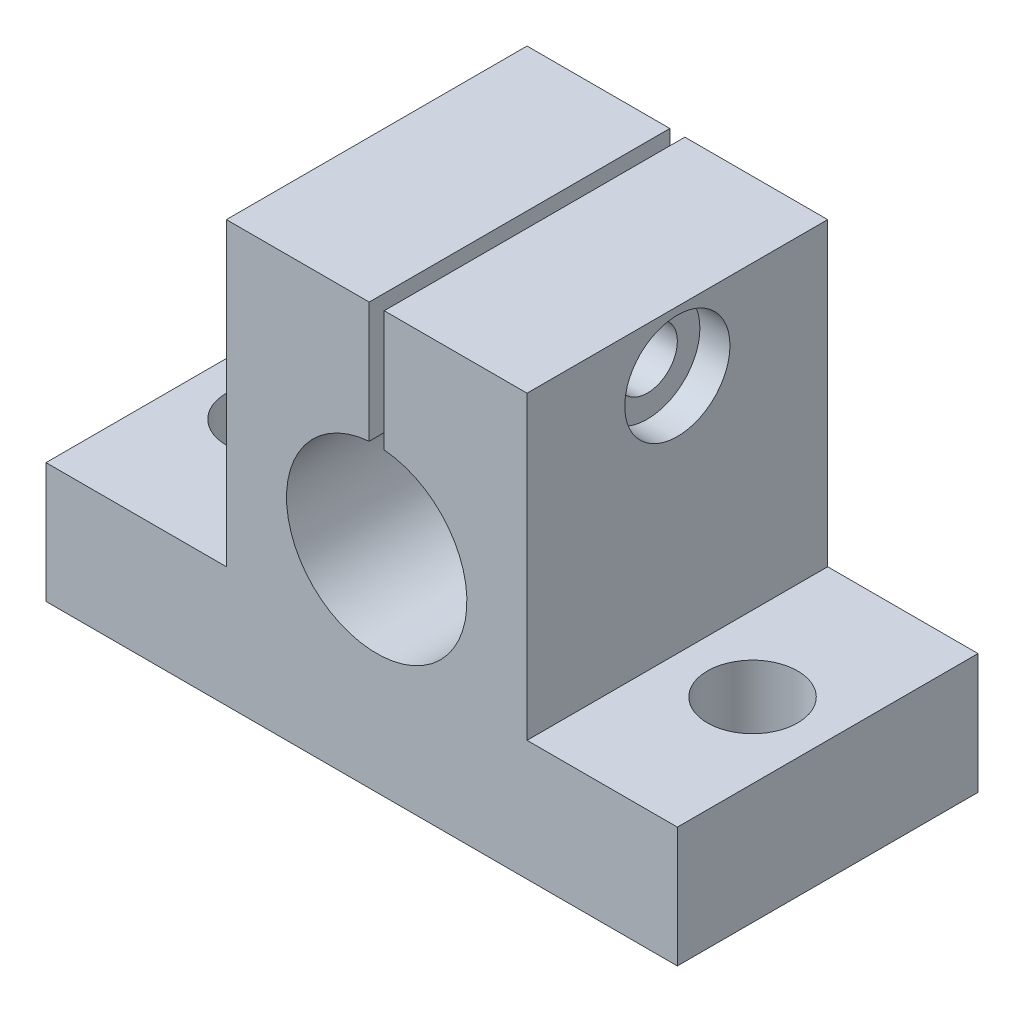
SolidWorks part; units mm, degrees
ref_plane "Спереди" through (0, 0, 0) normal (0, 0, 1) x (1, 0, 0)
ref_plane "Сверху" through (0, 0, 0) normal (0, 1, 0) x (1, 0, 0)
ref_plane "Справа" through (0, 0, 0) normal (1, 0, 0) x (0, 0, -1)
sketch "Эскиз1" plane through (0, 0, 0) normal (0, 0, 1) x (1, 0, 0)
  line L0 (0, 0) -> (0, 14) construction
  line L1 (-22, 0) -> (20, 0)
  line L2 (20, 0) -> (20, 8)
  line L3 (20, 8) -> (10, 8)
  line L4 (10, 8) -> (10, 28)
  line L5 (10, 28) -> (0.5, 28)
  line L6 (0.5, 28) -> (0.5, 19.9791)
  line L7 (-0.5, 19.9791) -> (-0.5, 28)
  line L8 (-0.5, 28) -> (-10, 28)
  line L9 (-10, 28) -> (-10, 8)
  line L10 (-10, 8) -> (-22, 8)
  line L11 (-22, 8) -> (-22, 0)
  arc A0 (-0.5, 19.9791) -> (0.5, 19.9791) centre (0, 14) ccw
  dimension "D1" = 6
  dimension "D2" = 1
  dimension "D3" = 8
  dimension "D4" = 42
  dimension "D5" = 14
  dimension "D6" = 20
  dimension "D7" = 14
  dimension "D8" = 6
extrude "Бобышка-Вытянуть1" add sketch "Эскиз1" along normal blind 20
sketch "Эскиз4" plane through (0, 8, 0) normal (0, 1, 0) x (1, 0, 0)
  line L0 (20, -20) -> (10, -20) construction
  line L1 (-10, -20) -> (-22, -20) construction
  line L2 (20, -20) -> (20, 0) construction
  line L3 (-22, -20) -> (-22, 0) construction
  circle A0 centre (15, -10) radius 3
  circle A1 centre (-17, -10) radius 3
  dimension "D1" = 6
  dimension "D2" = 6
  dimension "D3" = 10
  dimension "D4" = 10
  dimension "D5" = 5
  dimension "D6" = 5
extrude "Вырез-Вытянуть1" cut sketch "Эскиз4" against normal up to surface (8 mm away) up to face at (-1, 0, 10)
sketch "Эскиз5" plane through (10, 0, 0) normal (1, 0, 0) x (0, 0, -1)
  line L0 (-20, 8) -> (-20, 28) construction
  line L1 (-20, 28) -> (0, 28) construction
  circle A0 centre (-10, 24) radius 2
  dimension "D1" = 4
  dimension "D2" = 10
  dimension "D3" = 4
extrude "Вырез-Вытянуть2" cut sketch "Эскиз5" against normal up to surface (20 mm away) up to face at (-10, 18, 10)
sketch "Эскиз6" plane through (10, 0, 0) normal (1, 0, 0) x (0, 0, -1)
  circle A0 centre (-10, 24) radius 3.5
  dimension "D1" = 7
extrude "Вырез-Вытянуть3" cut sketch "Эскиз6" against normal blind 2
sketch "Эскиз7" plane through (-10, 0, 0) normal (-1, 0, 0) x (0, 0, 1)
  line L0 (20, 28) -> (0, 28) construction
  line L1 (14.0415, 24) -> (12.0207, 27.5)
  line L2 (12.0207, 27.5) -> (7.9793, 27.5)
  line L3 (7.9793, 27.5) -> (5.9585, 24)
  line L4 (5.9585, 24) -> (7.9793, 20.5)
  line L5 (7.9793, 20.5) -> (12.0207, 20.5)
  line L6 (12.0207, 20.5) -> (14.0415, 24)
  circle A0 centre (10, 24) radius 3.5 construction
  dimension "D1" = 7
extrude "Вырез-Вытянуть4" cut sketch "Эскиз7" against normal blind 3
